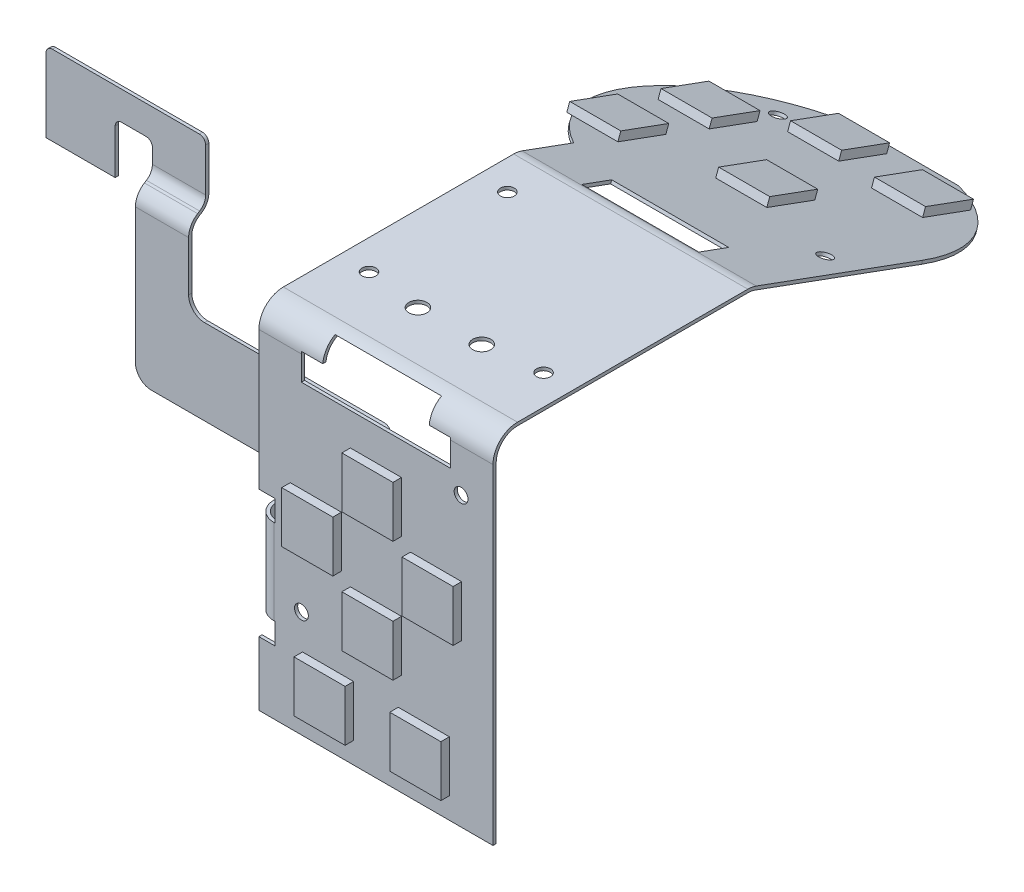
SolidWorks part; units mm, degrees
ref_plane "前视基准面" through (0, 0, 0) normal (0, 0, 1) x (1, 0, 0)
ref_plane "上视基准面" through (0, 0, 0) normal (0, 1, 0) x (1, 0, 0)
ref_plane "右视基准面" through (0, 0, 0) normal (1, 0, 0) x (0, 0, -1)
other "Configuration Table"
sketch "草图1" plane through (0, 0, 0) normal (1, 0, 0) x (0, 0, -1)
  line L0 (0, -25) -> (0, -2)
  line L1 (2, 0) -> (23.6457, 0)
  line L2 (24.3327, -0.1217) -> (52.1746, -10.3049)
  line L3 (-0.3, -25) -> (-0.3, -2)
  line L4 (2, 0.3) -> (23.6457, 0.3)
  line L5 (24.4358, 0.1601) -> (52.2777, -10.0231)
  line L6 (0, -25) -> (-0.3, -25)
  line L7 (52.2777, -10.0231) -> (52.1746, -10.3049)
  arc A0 (23.6457, 0) -> (24.3327, -0.1217) centre (23.6457, -2) cw
  arc A1 (0, -2) -> (2, 0) centre (2, -2) cw
  arc A2 (-0.3, -2) -> (2, 0.3) centre (2, -2) cw
  arc A3 (23.6457, 0.3) -> (24.4358, 0.1601) centre (23.6457, -2) cw
  point P7 (24, 0)
  point P10 (0, 0)
  point P19 (0, 0)
  dimension "D5" = 2
  dimension "D1" = 25
  dimension "D2" = 24
  dimension "D3" = 159.91
  dimension "D4" = 30
  dimension "D6" = 0.3
extrude "凸台-拉伸1" add sketch "草图1" along normal blind 22
sketch "草图2" plane through (0, 0, 0.3) normal (0, 0, 1) x (1, 0, 0)
  line L0 (22, 0.3) -> (0, 0.3) construction
  line L1 (4, -4.3) -> (18, -4.3)
  line L2 (4, -4.3) -> (4, -1.8)
  line L3 (4, -1.8) -> (18, -1.8)
  line L4 (18, -4.3) -> (18, -1.8)
  line L5 (6, -1.8) -> (16, -1.8)
  line L6 (6, -1.8) -> (6, 0)
  line L7 (6, 0) -> (16, 0)
  line L8 (16, -1.8) -> (16, 0)
  line L10 (11, -26.5654) -> (11, 3.7124) construction
  line L12 (0, -2) -> (0, -25) construction
  line L13 (22, -2) -> (22, -25) construction
  line M13 (22, -2) -> (0, -2)
  dimension "D1" = 1.8
  dimension "D2" = 2.5
  dimension "D3" = 0.3
  dimension "D4" = 14
  dimension "D5" = 10
extrude "切除-拉伸1" cut sketch "草图2" against normal blind 4 contours L3 L10 L7 L6 | L10 L5 L8 L7 | L1 L10 L2 M13 | L10 L1 L4 M13 | L10 L3 L2 M13 | L10 L4 L3 L5 M13 region at (7.5, -3.15, 0.3) region at (14.5, -3.15, 0.3) region at (7.5, -1.9, 0.3) region at (14.5, -1.9, 0.3) region at (13.5, -0.9, 0.3) region at (8.5, -0.9, 0.3)
sketch "草图3" plane through (0, 8.024, -2.9348) normal (0, 0.9392, -0.3435) x (1, 0, 0)
  line L0 (22, 52.5397) -> (22, 22.894) construction
  line L1 (22, 52.5397) -> (0, 52.5397) construction
  circle A0 centre (8, 39.5397) radius 14
  line M2 (0, 52.5397) -> (0, 22.894)
  line M4 (22, 22.894) -> (22, 52.5397)
  line M5 (22, 52.5397) -> (0, 52.5397)
  dimension "D1" = 28
  dimension "D2" = 13
extrude "切除-拉伸2" cut sketch "草图3" against normal through all contours A0 M4 M5 | A0 M5 M2 region at (19.6053, -8.9881, -49.4478) region at (0.8895, -9.8577, -51.8254)
extrude "凸台-拉伸2" add sketch "草图3<3>" against normal blind 0.3
sketch "草图3<3>" plane through (0, 8.024, -2.9348) normal (0, 0.9392, -0.3435) x (1, 0, 0) same geometry as "草图3"
sketch "草图4" plane through (0, 0, 0.3) normal (0, 0, 1) x (1, 0, 0)
  line L0 (-5.9466, -15.4) -> (23.7502, -15.4) construction
  line L1 (8.6, -7.35) -> (13.4, -7.35)
  line L2 (8.6, -7.35) -> (8.6, -12.15)
  line L3 (8.6, -12.15) -> (13.4, -12.15)
  line L4 (13.4, -7.35) -> (13.4, -12.15)
  line L5 (11, -28.2671) -> (11, 2.5503) construction
  line L6 (0, -2) -> (0, -25) construction
  line L7 (22, -2) -> (22, -25) construction
  line L8 (22, -25) -> (0, -25) construction
  line L9 (8.6, -18.65) -> (13.4, -18.65)
  line L10 (8.6, -18.65) -> (8.6, -23.45)
  line L11 (8.6, -23.45) -> (13.4, -23.45)
  line L12 (13.4, -18.65) -> (13.4, -23.45)
  line L14 (2.95, -13) -> (7.75, -13)
  line L15 (2.95, -13) -> (2.95, -17.8)
  line L16 (2.95, -17.8) -> (7.75, -17.8)
  line L17 (7.75, -13) -> (7.75, -17.8)
  line L18 (14.25, -13) -> (19.05, -13)
  line L19 (14.25, -13) -> (14.25, -17.8)
  line L20 (14.25, -17.8) -> (19.05, -17.8)
  line L21 (19.05, -13) -> (19.05, -17.8)
  dimension "D1" = 4.8
  dimension "D2" = 9.6
  dimension "D3" = 6.5
  dimension "D4" = 6.5
extrude "凸台-拉伸3" add sketch "草图4" along normal blind 0.8
sketch "草图5" plane through (0, 0.3, 0) normal (0, 1, 0) x (1, 0, 0)
  line L0 (11, -6.2283) -> (11, 16.6274) construction
  line L3 (0, 23.6457) -> (0, 2) construction
  line L4 (22, 23.6457) -> (22, 2) construction
  line L5 (22, 23.6457) -> (0, 23.6457) construction
  circle A0 centre (8, 6.6457) radius 0.85
  circle A1 centre (14, 6.6457) radius 0.85
  dimension "D1" = 1.7
  dimension "D2" = 17
  dimension "D3" = 3
extrude "切除-拉伸3" cut sketch "草图5" against normal through all
sketch "草图6" plane through (0, 8.024, -2.9348) normal (0, 0.9392, -0.3435) x (1, 0, 0)
  line L0 (11, 16.3664) -> (11, 30.7303) construction
  line L1 (5.5, 23) -> (16.5, 23)
  line L2 (5.5, 23) -> (5.5, 26)
  line L3 (5.5, 26) -> (16.5, 26)
  line L4 (16.5, 23) -> (16.5, 26)
  line L7 (0, 22.1039) -> (0, 1.7753) construction
  line L8 (22, 22.1039) -> (22, 1.7753) construction
  dimension "D1" = 11
  dimension "D2" = 3
  dimension "D3" = 23
extrude "切除-拉伸4" cut sketch "草图6" against normal blind 1
sketch "草图7" plane through (0, 8.024, -2.9348) normal (0, 0.9392, -0.3435) x (1, 0, 0)
  line L1 (7.3385, 34.4514) -> (12.1385, 34.4514)
  line L2 (7.3385, 34.4514) -> (7.3385, 39.2514)
  line L3 (7.3385, 39.2514) -> (12.1385, 39.2514)
  line L4 (12.1385, 34.4514) -> (12.1385, 39.2514)
  line L5 (11.7188, 45.3744) -> (16.5188, 45.3744)
  line L6 (11.7188, 45.3744) -> (11.7188, 50.1744)
  line L7 (11.7188, 50.1744) -> (16.5188, 50.1744)
  line L8 (16.5188, 45.3744) -> (16.5188, 50.1744)
  line L9 (7.6196, 46.4557) -> (2.8196, 46.4557)
  line L10 (7.6196, 46.4557) -> (7.6196, 51.2557)
  line L11 (7.6196, 51.2557) -> (2.8196, 51.2557)
  line L12 (2.8196, 46.4557) -> (2.8196, 51.2557)
  line L13 (0.9105, 40.6376) -> (-3.8895, 40.6376)
  line L14 (0.9105, 40.6376) -> (0.9105, 45.4376)
  line L15 (0.9105, 45.4376) -> (-3.8895, 45.4376)
  line L16 (-3.8895, 40.6376) -> (-3.8895, 45.4376)
  line L17 (0.748, 31.6791) -> (-4.052, 31.6791)
  line L18 (0.748, 31.6791) -> (0.748, 36.4791)
  line L19 (0.748, 36.4791) -> (-4.052, 36.4791)
  line L20 (-4.052, 31.6791) -> (-4.052, 36.4791)
  dimension "D1" = 4.8
extrude "凸台-拉伸4" add sketch "草图7" along normal blind 0.8
sketch "草图9" plane through (0, -25, 0) normal (0, -1, 0) x (1, 0, 0)
  line L0 (22, 0.3) -> (0, 0.3) construction
  line L1 (0, 0) -> (1.5, 0)
  line L2 (0, 0) -> (0, 0.3)
  line L3 (0, 0.3) -> (1.5, 0.3)
  line L4 (1.5, 0) -> (1.5, 0.3)
  dimension "D1" = 1.5
extrude "切除-拉伸5" cut sketch "草图9" against normal blind 10
sketch "草图10" plane through (0, -25, 0) normal (0, -1, 0) x (1, 0, 0)
  line L0 (1.5, 0) -> (1.4, 0)
  line L1 (-0.1, -1.5) -> (-0.1, -11.5)
  line L2 (-1.6, -13) -> (-17.6, -13)
  line L3 (1.5, 0.3) -> (1.4, 0.3)
  line L4 (-0.4, -1.5) -> (-0.4, -11.5)
  line L5 (-1.6, -12.7) -> (-17.6, -12.7)
  line L6 (1.5, 0) -> (1.5, 0.3)
  line L7 (-17.6, -13) -> (-17.6, -12.7)
  arc A0 (1.4, 0) -> (-0.1, -1.5) centre (1.4, -1.5) ccw
  arc A1 (-0.1, -11.5) -> (-1.6, -13) centre (-1.6, -11.5) cw
  arc A2 (1.4, 0.3) -> (-0.4, -1.5) centre (1.4, -1.5) ccw
  arc A3 (-0.4, -11.5) -> (-1.6, -12.7) centre (-1.6, -11.5) cw
  point P8 (-0.1, 0)
  point P11 (-0.1, -13)
  dimension "D3" = 1.5
  dimension "D1" = 1.6
  dimension "D2" = 13
  dimension "D5" = 16
  dimension "D4" = 0.3
extrude "凸台-拉伸5" add sketch "草图10" against normal blind 8
sketch "草图11" plane through (0, 0, -12.7) normal (0, 0, 1) x (1, 0, 0)
  line L0 (-17.6, -17) -> (-17.6, -25)
  line L1 (-17.6, -25) -> (-23.1, -25)
  line L2 (-24.6, -23.5) -> (-24.6, -11)
  line L3 (-24.6, -11) -> (-19.6, -11)
  line L4 (-19.6, -11) -> (-19.6, -15.5)
  line L5 (-18.1, -17) -> (-17.6, -17)
  arc A0 (-23.1, -25) -> (-24.6, -23.5) centre (-23.1, -23.5) cw
  arc A1 (-19.6, -15.5) -> (-18.1, -17) centre (-18.1, -15.5) ccw
  point P10 (-24.6, -25)
  dimension "D4" = 1.5
  dimension "D1" = 7
  dimension "D2" = 14
  dimension "D3" = 5
extrude "凸台-拉伸6" add sketch "草图11" against normal blind 0.3
sketch "草图12" plane through (-24.6, 0, 0) normal (-1, 0, 0) x (0, 0, 1)
  line L0 (-13, -11) -> (-13, -10.8314)
  line L1 (-13.705, -9.5594) -> (-13.895, -9.4406)
  line L2 (-14.6, -8.1686) -> (-14.6, -8)
  line L3 (-12.7, -11) -> (-12.7, -10.8314)
  line L4 (-13.546, -9.305) -> (-13.736, -9.1862)
  line L5 (-14.3, -8.1686) -> (-14.3, -8)
  line L6 (-13, -11) -> (-12.7, -11)
  line L7 (-14.6, -8) -> (-14.3, -8)
  arc A0 (-13, -10.8314) -> (-13.705, -9.5594) centre (-14.5, -10.8314) ccw
  arc A1 (-13.895, -9.4406) -> (-14.6, -8.1686) centre (-13.1, -8.1686) cw
  arc A2 (-12.7, -10.8314) -> (-13.546, -9.305) centre (-14.5, -10.8314) ccw
  arc A3 (-13.736, -9.1862) -> (-14.3, -8.1686) centre (-13.1, -8.1686) cw
  point P8 (-13, -10)
  point P11 (-14.6, -9)
  dimension "D5" = 1.5
  dimension "D1" = 1
  dimension "D2" = 1
  dimension "D3" = 1.6
  dimension "D4" = 1
  dimension "D6" = 0.3
extrude "凸台-拉伸7" add sketch "草图12" against normal blind 5
sketch "草图13" plane through (0, 0, -14.3) normal (0, 0, 1) x (1, 0, 0)
  line L0 (-24.6, -8) -> (-19.6, -8)
  line L1 (-19.6, -8) -> (-19.6, -4.1)
  line L2 (-20.2, -3.5) -> (-34, -3.5)
  line L3 (-34.6, -4.1) -> (-34.6, -11)
  line L4 (-34.6, -11) -> (-28.1, -11)
  line L5 (-28.1, -11) -> (-28.1, -6.8)
  line L6 (-27.5, -6.2) -> (-25.2, -6.2)
  line L7 (-24.6, -6.8) -> (-24.6, -8)
  arc A0 (-34, -3.5) -> (-34.6, -4.1) centre (-34, -4.1) ccw
  arc A1 (-19.6, -4.1) -> (-20.2, -3.5) centre (-20.2, -4.1) ccw
  arc A2 (-25.2, -6.2) -> (-24.6, -6.8) centre (-25.2, -6.8) cw
  arc A3 (-28.1, -6.8) -> (-27.5, -6.2) centre (-27.5, -6.8) cw
  point P12 (-34.6, -3.5)
  point P15 (-19.6, -3.5)
  point P18 (-24.6, -6.2)
  dimension "D5" = 0.6
  dimension "D1" = 4.5
  dimension "D2" = 6.5
  dimension "D3" = 7.5
  dimension "D4" = 1.8
  dimension "D6" = 15
extrude "凸台-拉伸8" add sketch "草图13" against normal blind 0.3
sketch "草图14" plane through (0, 8.024, -2.9348) normal (0, 0.9392, -0.3435) x (1, 0, 0)
  line L0 (0, 28.0506) -> (0, 22.894) construction
  line L1 (2, 52.5506) -> (14, 52.5506)
  line L2 (2, 52.5506) -> (2, 54.5506)
  line L3 (2, 54.5506) -> (14, 54.5506)
  line L4 (14, 52.5506) -> (14, 54.5506)
  circle A0 centre (0.5, 47.9506) radius 0.65
  circle A1 centre (19.5, 32.4506) radius 0.65
  dimension "D5" = 1.3
  dimension "D1" = 12
  dimension "D2" = 2
  dimension "D3" = 24.5
  dimension "D4" = 2
  dimension "D6" = 0.5
  dimension "D7" = 19.9
  dimension "D8" = 19
  dimension "D9" = 15.5
extrude "切除-拉伸6" cut sketch "草图14" against normal blind 4
sketch "草图15" plane through (0, 0.3, 0) normal (0, 1, 0) x (1, 0, 0)
  line L0 (2.8, 18.5921) -> (2.8, 10.622) construction
  line L1 (15.631, 7.25) -> (4.6393, 7.25) construction
  line L4 (11, -5.7583) -> (11, 19.5262) construction
  line L5 (0, 23.6457) -> (0, 2) construction
  line L6 (22, 23.6457) -> (22, 2) construction
  line L7 (22, 2) -> (0, 2) construction
  circle A0 centre (2.8, 20.25) radius 0.65
  circle A1 centre (2.8, 7.25) radius 0.65
  circle A2 centre (19.2, 7.25) radius 0.65
  dimension "D1" = 1.3
  dimension "D2" = 13
  dimension "D3" = 16.4
  dimension "D4" = 5.25
extrude "切除-拉伸7" cut sketch "草图15" against normal blind 4
sketch "草图16" plane through (0, 0, 0.3) normal (0, 0, 1) x (1, 0, 0)
  line L0 (22, -2) -> (22, -25) construction
  line L1 (22, -2) -> (18, -2) construction
  circle A0 centre (19, -6) radius 0.65
  circle A1 centre (4, -23) radius 0.65
  dimension "D1" = 1.3
  dimension "D2" = 3
  dimension "D3" = 4
  dimension "D4" = 15
  dimension "D5" = 17
extrude "切除-拉伸8" cut sketch "草图16" against normal blind 4
sketch "草图17" plane through (0, 0, 0.3) normal (0, 0, 1) x (1, 0, 0)
  line L0 (22, -25) -> (22, -33)
  line L1 (22, -33) -> (0, -33)
  line L2 (0, -33) -> (0, -27)
  line L3 (0, -27) -> (1.5, -27)
  line L4 (1.5, -27) -> (1.5, -25)
  line L5 (22, -25) -> (1.4, -25) construction
  line L6 (1.5, -25) -> (22, -25)
  line L7 (1.5, -15) -> (1.5, -17) construction
  dimension "D1" = 2
  dimension "D2" = 8
extrude "凸台-拉伸9" add sketch "草图17" against normal blind 0.3
sketch "草图18" plane through (0, 0, 0.3) normal (0, 0, 1) x (1, 0, 0)
  line L0 (11, -23.45) -> (11, -36.7361) construction
  line L1 (4.1, -31) -> (8.9, -31)
  line L2 (4.1, -31) -> (4.1, -26.2)
  line L3 (4.1, -26.2) -> (8.9, -26.2)
  line L4 (8.9, -31) -> (8.9, -26.2)
  line L5 (13.1, -31) -> (17.9, -31)
  line L6 (13.1, -31) -> (13.1, -26.2)
  line L7 (13.1, -26.2) -> (17.9, -26.2)
  line L8 (17.9, -31) -> (17.9, -26.2)
  line L10 (0, -33) -> (22, -33) construction
  point P9 (0, 0)
  dimension "D1" = 4.8
  dimension "D2" = 4.2
  dimension "D3" = 2
extrude "凸台-拉伸10" add sketch "草图18" along normal blind 0.8
